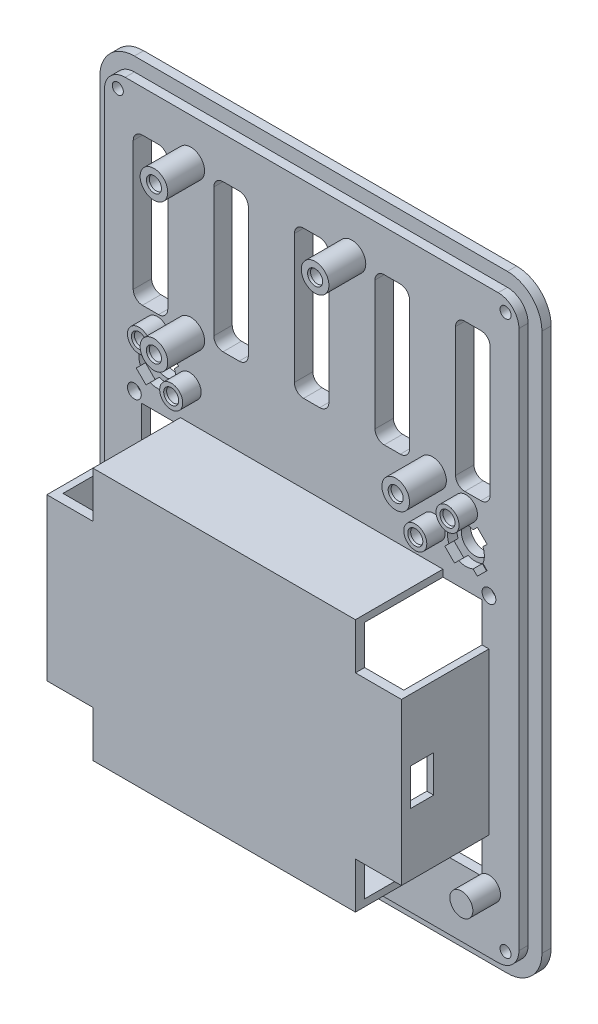
SolidWorks part; units mm, degrees
note: The reader was unsure of these and kept them because the rebuilt part matched: shared geometry of "Sketch8<3>", "Sketch17<3>", "Sketch16<3>".
ref_plane "Front Plane" through (0, 0, 0) normal (0, 0, 1) x (1, 0, 0)
ref_plane "Top Plane" through (0, 0, 0) normal (0, 1, 0) x (1, 0, 0)
ref_plane "Right Plane" through (0, 0, 0) normal (1, 0, 0) x (0, 0, -1)
sketch "Sketch2" plane through (0, 0, 0) normal (0, 0, 1) x (1, 0, 0)
  line L20 (45, -58.5) -> (45, 58.5)
  line L21 (-40.5, -63) -> (40.5, -63)
  line L22 (-45, 58.5) -> (-45, -58.5)
  line L23 (40.5, 63) -> (-40.5, 63)
  line L24 (45, -58.5) -> (45, 58.5)
  line L25 (-40.5, -63) -> (40.5, -63)
  line L26 (-45, 58.5) -> (-45, -58.5)
  line L27 (40.5, 63) -> (-40.5, 63)
  arc A24 (40.5, -63) -> (45, -58.5) centre (40.5, -58.5) ccw
  arc A25 (-45, -58.5) -> (-40.5, -63) centre (-40.5, -58.5) ccw
  arc A26 (-40.5, 63) -> (-45, 58.5) centre (-40.5, 58.5) ccw
  arc A27 (45, 58.5) -> (40.5, 63) centre (40.5, 58.5) ccw
  arc A28 (40.5, -63) -> (45, -58.5) centre (40.5, -58.5) ccw
  arc A29 (-45, -58.5) -> (-40.5, -63) centre (-40.5, -58.5) ccw
  arc A30 (-40.5, 63) -> (-45, 58.5) centre (-40.5, 58.5) ccw
  arc A31 (45, 58.5) -> (40.5, 63) centre (40.5, 58.5) ccw
  dimension "D1" = 3
extrude "Boss-Extrude1" add sketch "Sketch2" along normal blind 2
sketch "Sketch3" plane through (0, 0, 0) normal (0, 0, -1) x (-1, 0, 0)
  line L8 (-40.5, -66) -> (40.5, -66)
  line L9 (48, -58.5) -> (48, 58.5)
  line L10 (40.5, 66) -> (-40.5, 66)
  line L11 (-48, 58.5) -> (-48, -58.5)
  line L12 (-40.5, -66) -> (40.5, -66)
  line L13 (48, -58.5) -> (48, 58.5)
  line L14 (40.5, 66) -> (-40.5, 66)
  line L15 (-48, 58.5) -> (-48, -58.5)
  arc A8 (-48, -58.5) -> (-40.5, -66) centre (-40.5, -58.5) ccw
  arc A9 (40.5, -66) -> (48, -58.5) centre (40.5, -58.5) ccw
  arc A10 (48, 58.5) -> (40.5, 66) centre (40.5, 58.5) ccw
  arc A11 (-40.5, 66) -> (-48, 58.5) centre (-40.5, 58.5) ccw
  arc A12 (-48, -58.5) -> (-40.5, -66) centre (-40.5, -58.5) ccw
  arc A13 (40.5, -66) -> (48, -58.5) centre (40.5, -58.5) ccw
  arc A14 (48, 58.5) -> (40.5, 66) centre (40.5, 58.5) ccw
  arc A15 (-40.5, 66) -> (-48, 58.5) centre (-40.5, 58.5) ccw
  dimension "D1" = 3
extrude "Boss-Extrude2" add sketch "Sketch3" along normal blind 2
sketch "Sketch5" plane through (0, 0, -2) normal (0, 0, -1) x (-1, 0, 0)
  line L0 (-48, 38) -> (48, 38) construction
  line L1 (-36.75, 22) -> (-33.25, 22)
  line L2 (-38.75, 24) -> (-38.75, 52)
  line L3 (-36.75, 54) -> (-33.25, 54)
  line L4 (-31.25, 24) -> (-31.25, 52)
  line L5 (-38.75, 22) -> (-31.25, 54) construction
  line L6 (-38.75, 54) -> (-31.25, 22) construction
  line L7 (-48, 58.5) -> (-48, -58.5) construction
  line L8 (48, -58.5) -> (48, 58.5) construction
  line L9 (40.5, 66) -> (-40.5, 66) construction
  line L10 (-21.25, 24) -> (-21.25, 52)
  line L11 (-13.75, 24) -> (-13.75, 52)
  line L12 (-19.25, 54) -> (-15.75, 54)
  line L13 (-19.25, 22) -> (-15.75, 22)
  line L14 (-21.25, 54) -> (-13.75, 22) construction
  line L15 (-21.25, 22) -> (-13.75, 54) construction
  line L16 (-3.75, 24) -> (-3.75, 52)
  line L17 (3.75, 24) -> (3.75, 52)
  line L18 (-1.75, 54) -> (1.75, 54)
  line L19 (-1.75, 22) -> (1.75, 22)
  line L20 (-3.75, 54) -> (3.75, 22) construction
  line L21 (-3.75, 22) -> (3.75, 54) construction
  line L22 (13.75, 24) -> (13.75, 52)
  line L23 (21.25, 24) -> (21.25, 52)
  line L24 (15.75, 54) -> (19.25, 54)
  line L25 (15.75, 22) -> (19.25, 22)
  line L26 (13.75, 54) -> (21.25, 22) construction
  line L27 (13.75, 22) -> (21.25, 54) construction
  line L28 (31.25, 24) -> (31.25, 52)
  line L29 (38.75, 24) -> (38.75, 52)
  line L30 (33.25, 54) -> (36.75, 54)
  line L31 (33.25, 22) -> (36.75, 22)
  line L32 (31.25, 54) -> (38.75, 22) construction
  line L33 (31.25, 22) -> (38.75, 54) construction
  line L34 (-3.5, 66) -> (-3.5, 34) construction
  arc A0 (31.25, 52) -> (33.25, 54) centre (33.25, 52) cw
  arc A1 (38.75, 52) -> (36.75, 54) centre (36.75, 52) ccw
  arc A2 (38.75, 24) -> (36.75, 22) centre (36.75, 24) cw
  arc A3 (31.25, 24) -> (33.25, 22) centre (33.25, 24) ccw
  arc A4 (13.75, 24) -> (15.75, 22) centre (15.75, 24) ccw
  arc A5 (21.25, 24) -> (19.25, 22) centre (19.25, 24) cw
  arc A6 (21.25, 52) -> (19.25, 54) centre (19.25, 52) ccw
  arc A7 (13.75, 52) -> (15.75, 54) centre (15.75, 52) cw
  arc A8 (3.75, 24) -> (1.75, 22) centre (1.75, 24) cw
  arc A9 (-3.75, 24) -> (-1.75, 22) centre (-1.75, 24) ccw
  arc A10 (3.75, 52) -> (1.75, 54) centre (1.75, 52) ccw
  arc A11 (-3.75, 52) -> (-1.75, 54) centre (-1.75, 52) cw
  arc A12 (-21.25, 24) -> (-19.25, 22) centre (-19.25, 24) ccw
  arc A13 (-13.75, 24) -> (-15.75, 22) centre (-15.75, 24) cw
  arc A14 (-13.75, 52) -> (-15.75, 54) centre (-15.75, 52) ccw
  arc A15 (-21.25, 52) -> (-19.25, 54) centre (-19.25, 52) cw
  arc A16 (-33.25, 22) -> (-31.25, 24) centre (-33.25, 24) ccw
  arc A17 (-36.75, 22) -> (-38.75, 24) centre (-36.75, 24) cw
  arc A18 (-33.25, 54) -> (-31.25, 52) centre (-33.25, 52) cw
  arc A19 (-38.75, 52) -> (-36.75, 54) centre (-36.75, 52) cw
  point P0 (-35, 38)
  point P13 (-17.5, 38)
  point P19 (0, 38)
  point P24 (17.5, 38)
  point P29 (35, 38)
  dimension "D6" = 2
  dimension "D1" = 7.5
  dimension "D2" = 32
  dimension "D3" = 28
  dimension "D5" = 10
  dimension "D4" = 5
extrude "Cut-Extrude1" cut sketch "Sketch5" against normal through all
hole_wizard "CBORE for M2 Pan Head Machine Screw1" positions "Sketch7" profile "Sketch6" counterbore size "M2" standard "ANSI Metric" end condition through all
sketch "Sketch7" plane through (0, 0, -2) normal (0, 0, -1) x (-1, 0, 0)
  point P0 (-42.1, 60.1)
  point P3 (42.1, 60.1)
  point P6 (-42.1, -60.1)
  point P9 (42.1, -60.1)
sketch "Sketch6" plane through (42.1, 60.1, -2) normal (1, 0, 0) x (0, 1, 0)
  line L0 (0, 0) -> (0, 4)
  line L1 (0, 4) -> (1.2, 4)
  line L3 (1.2, 4) -> (1.2, 1.6)
  line L4 (1.2, 1.6) -> (2.5, 1.6)
  line L5 (2.5, 1.6) -> (2.5, 0)
  line L7 (2.5, 0) -> (0, 0)
  line L11 (0, -6.35) -> (0, 107.95) construction
  dimension "Thru Hole Dia." = 2.4
  dimension "Thru Hole Depth" = 4
  dimension "C'Bore Dia." = 5
  dimension "C'Bore Depth" = 1.6
sketch "Sketch8" plane through (0, 0, -2) normal (0, 0, -1) x (-1, 0, 0)
  line L0 (0, 66) -> (0, -66) construction
  line L1 (-37, 3.5) -> (37, 3.5)
  line L2 (-37, 3.5) -> (-37, -48.5)
  line L3 (-37, -48.5) -> (37, -48.5)
  line L4 (37, 3.5) -> (37, -48.5)
  line L5 (-37, 3.5) -> (37, -48.5) construction
  line L6 (-37, -48.5) -> (37, 3.5) construction
  line L7 (40.5, 66) -> (-40.5, 66) construction
  line L8 (-40.5, -66) -> (40.5, -66) construction
  line L9 (-38.5, 5) -> (38.5, 5)
  line L10 (38.5, 5) -> (38.5, -50)
  line L11 (-38.5, -50) -> (38.5, -50)
  line L12 (-38.5, 5) -> (-38.5, -50)
  point P0 (0, -22.5)
  dimension "D1" = 17.5
  dimension "D2" = 52
  dimension "D3" = 74
  dimension "D4" = 1.5
extrude "Boss-Extrude3" add sketch "Sketch8<3>" against normal blind 19 from surface at -4 contours L9 L10 L11 L12 starting at face at (40.9, 60.1, 2)
sketch "Sketch8<3>" plane through (0, 0, -2) normal (0, 0, -1) x (-1, 0, 0) same geometry as "Sketch8"
extrude "Cut-Extrude2" cut sketch "Sketch8" against normal blind 21 contours L1 L4 L3 L2
sketch "Sketch9" plane through (0, 0, -2) normal (0, 0, -1) x (-1, 0, 0)
  line L18 (-41, -52.5) -> (41, -52.5)
  line L19 (41, -52.5) -> (41, 7.5)
  line L20 (-41, 7.5) -> (-41, -52.5)
  line L21 (41, 7.5) -> (-41, 7.5)
  line L22 (-41, -52.5) -> (41, -52.5)
  line L23 (41, -52.5) -> (41, 7.5)
  line L24 (-41, 7.5) -> (-41, -52.5)
  line L25 (41, 7.5) -> (-41, 7.5)
  dimension "D1" = 4
extrude "Cut-Extrude3" cut sketch "Sketch9" against normal blind 2
sketch "Sketch10" plane through (0, 0, 2) normal (0, 0, 1) x (1, 0, 0)
  circle A0 centre (38.5, 5) radius 2.5
  circle A1 centre (-38.5, 5) radius 2.5
  circle A2 centre (-38.5, -50) radius 2.5
  circle A3 centre (38.5, -50) radius 2.5
  dimension "D1" = 5
sketch "Sketch30" plane through (0, 0, 2) normal (0, 0, 1) x (1, 0, 0)
  circle A0 centre (-38.5, 5) radius 1.5
  circle A1 centre (38.5, 5) radius 1.5
  dimension "D1" = 3
extrude "Cut-Extrude11" cut sketch "Sketch30" along normal blind 5 and the other way through all
sketch "Sketch15" plane through (38.5, 0, 0) normal (1, 0, 0) x (0, 0, -1)
  line L0 (-2, -22.5) -> (-21, -22.5) construction
  line L1 (-19, -18.5) -> (-14, -18.5)
  line L2 (-19, -18.5) -> (-19, -26.5)
  line L3 (-19, -26.5) -> (-14, -26.5)
  line L4 (-14, -18.5) -> (-14, -26.5)
  line L6 (-19, 3.5) -> (-19, -48.5) construction
  line L7 (-2, -50) -> (-2, 3.5) construction
  line L9 (-21, -50) -> (-21, 5) construction
  point P12 (-19, -22.5)
  dimension "D1" = 8
  dimension "D2" = 5
extrude "Cut-Extrude4" cut sketch "Sketch15" against normal through all
sketch "Sketch16" plane through (0, 0, -2) normal (0, 0, -1) x (-1, 0, 0)
  line L0 (2.5158, -57.4) -> (-2.5158, -57.4)
  line L1 (-4, -54.9) -> (-4, -55.719)
  line L2 (3.5, -54.4) -> (-3.5, -54.4)
  line L3 (4, -54.9) -> (4, -55.719)
  line L4 (0, -54.4) -> (0, -57.4) construction
  line L5 (-3.8841, -56.0391) -> (-2.8999, -57.2201)
  line L6 (3.8841, -56.0391) -> (2.8999, -57.2201)
  line L7 (0, 66) -> (0, -66) construction
  line L8 (40.5, 66) -> (-40.5, 66) construction
  line L9 (-40.5, -66) -> (40.5, -66) construction
  line L10 (40.5, -63) -> (-40.5, -63) construction
  line L12 (6.5, -59.2) -> (-6.5, -59.2)
  line L13 (6.5, -59.2) -> (6.5, -53.4)
  line L14 (6.5, -53.4) -> (-6.5, -53.4)
  line L15 (-6.5, -59.2) -> (-6.5, -53.4)
  line L16 (6.5, -59.2) -> (-6.5, -53.4) construction
  line L17 (6.5, -53.4) -> (-6.5, -59.2) construction
  arc A0 (-4, -55.719) -> (-3.8841, -56.0391) centre (-3.5, -55.719) ccw
  arc A1 (-2.5158, -57.4) -> (-2.8999, -57.2201) centre (-2.5158, -56.9) cw
  arc A2 (2.5158, -57.4) -> (2.8999, -57.2201) centre (2.5158, -56.9) ccw
  arc A3 (4, -55.719) -> (3.8841, -56.0391) centre (3.5, -55.719) cw
  arc A4 (4, -54.9) -> (3.5, -54.4) centre (3.5, -54.9) ccw
  arc A5 (-3.5, -54.4) -> (-4, -54.9) centre (-3.5, -54.9) ccw
  point P7 (0, -55.9)
  point P19 (-4, -55.9)
  point P22 (-2.75, -57.4)
  point P25 (2.75, -57.4)
  point P30 (4, -54.4)
  point P33 (-4, -54.4)
  point P34 (0, -55.9)
  point P39 (0, -56.3)
  point P40 (0, -56.3)
  point P41 (0, -56.3)
  dimension "D6" = 0.5
  dimension "D8" = 13
  dimension "D7" = 1.8
  dimension "D1" = 8
  dimension "D2" = 5.5
  dimension "D3" = 3
  dimension "D4" = 1.5
  dimension "D5" = 5.6
  dimension "D9" = 1
extrude "Cut-Extrude5" cut sketch "Sketch16" against normal through all contours L2 A5 L1 A0 L5 A1 L0 A2 L6 A3 L3 A4
sketch "Sketch17" plane through (0, 0, 0) normal (0, 0, -1) x (-1, 0, 0)
  line L0 (-28.9038, 9.5251) -> (-29.8173, 10.4386)
  line L1 (38.0962, 9.5251) -> (37.1827, 10.4386)
  line L2 (38.0962, 9.5251) -> (35.9749, 7.4038)
  line L3 (31.0251, 16.5962) -> (28.9038, 14.4749)
  line L4 (37.1827, 13.5614) -> (38.0962, 14.4749)
  line L5 (35.9749, 7.4038) -> (35.0614, 8.3173)
  line L6 (31.9386, 15.6827) -> (31.0251, 16.5962)
  line L7 (38.0962, 9.5251) -> (28.9038, 14.4749) construction
  line L8 (35.0614, 15.6827) -> (35.9749, 16.5962)
  line L9 (31.0251, 16.5962) -> (35.9749, 7.4038) construction
  line L10 (29.9376, 12) -> (-56.7892, 12) construction
  line L11 (28.9038, 9.5251) -> (29.8173, 10.4386)
  line L12 (28.9038, 9.5251) -> (31.0251, 7.4038)
  line L13 (35.9749, 16.5962) -> (38.0962, 14.4749)
  line L14 (31.0251, 7.4038) -> (31.9386, 8.3173)
  line L15 (28.9038, 9.5251) -> (38.0962, 14.4749) construction
  line L16 (35.9749, 16.5962) -> (31.0251, 7.4038) construction
  line L17 (-28.9038, 9.5251) -> (-31.0251, 7.4038)
  line L18 (33.5, 5) -> (33.5, 12) construction
  line L19 (37, 5) -> (-37, 5) construction
  line L20 (29.8173, 13.5614) -> (28.9038, 14.4749)
  line L21 (-35.9749, 16.5962) -> (-38.0962, 14.4749)
  line L22 (-31.0251, 7.4038) -> (-31.9386, 8.3173)
  line L23 (-28.9038, 9.5251) -> (-38.0962, 14.4749) construction
  line L24 (-35.9749, 16.5962) -> (-31.0251, 7.4038) construction
  line L25 (-35.9749, 7.4038) -> (-35.0614, 8.3173)
  line L26 (-35.9749, 7.4038) -> (-38.0962, 9.5251)
  line L27 (-28.9038, 14.4749) -> (-31.0251, 16.5962)
  line L28 (-38.0962, 9.5251) -> (-37.1827, 10.4386)
  line L29 (-35.9749, 7.4038) -> (-31.0251, 16.5962) construction
  line L30 (-28.9038, 14.4749) -> (-38.0962, 9.5251) construction
  line L31 (-29.8173, 13.5614) -> (-28.9038, 14.4749)
  line L32 (-35.0614, 15.6827) -> (-35.9749, 16.5962)
  line L33 (-37.1827, 13.5614) -> (-38.0962, 14.4749)
  line L34 (-31.9386, 15.6827) -> (-31.0251, 16.5962)
  line L35 (-33.5, 5) -> (-33.5, 12) construction
  line L36 (37, 5) -> (-37, 5) construction
  line L37 (-38.5, -50) -> (-38.5, 3.5) construction
  circle A0 centre (33.5, 12) radius 3
  circle A1 centre (-33.5, 12) radius 3
  arc A2 (29.8173, 13.5614) -> (29.8173, 10.4386) centre (33.5, 12) ccw
  arc A3 (37.1827, 10.4386) -> (37.1827, 13.5614) centre (33.5, 12) ccw
  circle A4 centre (33.5, 12) radius 4 construction
  arc A5 (35.0614, 15.6827) -> (31.9386, 15.6827) centre (33.5, 12) ccw
  arc A6 (31.9386, 8.3173) -> (35.0614, 8.3173) centre (33.5, 12) ccw
  arc A7 (-31.9386, 15.6827) -> (-35.0614, 15.6827) centre (-33.5, 12) ccw
  arc A8 (-29.8173, 10.4386) -> (-29.8173, 13.5614) centre (-33.5, 12) ccw
  circle A9 centre (-33.5, 12) radius 4 construction
  arc A10 (-37.1827, 13.5614) -> (-37.1827, 10.4386) centre (-33.5, 12) ccw
  arc A11 (-35.0614, 8.3173) -> (-31.9386, 8.3173) centre (-33.5, 12) ccw
  arc A12 (38.5, 3.5) -> (37, 5) centre (38.5, 5) ccw construction
  point P9 (33.5, 12)
  point P13 (40.5, -3)
  point P18 (-33.5, 12)
  point P20 (-38.5, 12)
  point P23 (42.3252, 13.1695)
  point P25 (44, -3)
  point P34 (-36, -3)
  point P36 (-34.2282, 12)
  dimension "D2" = 6
  dimension "D1" = 3
  dimension "D3" = 10
  dimension "D4" = 1
  dimension "D5" = 45
  dimension "D7" = 45
  dimension "D8" = 1
  dimension "D9" = 10
  dimension "D10" = 10
  dimension "D11" = 5
  dimension "D6" = 7
  dimension "D12" = 5
extrude "Cut-Extrude7" cut sketch "Sketch17" along normal up to surface (2 mm away) and the other way through all contours A0 | A1 up to face at (0, -55.9379, -2)
extrude "Cut-Extrude8" cut sketch "Sketch17<3>" along normal blind 2 from surface at -2 starting at face at (36.5, 12, 2)
sketch "Sketch17<3>" plane through (0, 0, 0) normal (0, 0, -1) x (-1, 0, 0) same geometry as "Sketch17"
sketch "Sketch18" [suppressed] plane through (0, 0, 2) normal (0, 0, 1) x (1, 0, 0)
  line L0 (-40.5, 5) -> (-40.5, -11) construction
  line L1 (-40.5, 5) -> (40.5, 5) construction
  line L2 (-40.5, -11) -> (40.5, -11) construction
  line L3 (40.5, -11) -> (40.5, 5) construction
  circle A0 centre (-40.5, 5) radius 2.5
  circle A1 centre (-40.5, -11) radius 2.5
  circle A3 centre (40.5, 5) radius 2.5
  circle A4 centre (40.5, -11) radius 2.5
  point P5 (-40.5, -3)
  point P13 (40.5, -3)
  dimension "D1" = 5
  dimension "D2" = 16
  dimension "D3" = 8
extrude "Boss-Extrude5" [suppressed] add sketch "Sketch18" along normal blind 4
hole_wizard "CSK for M2 Flat Head Machine Screw4" [suppressed] positions "3DSketch2" profile "Sketch20" countersink size "M2" standard "ANSI Metric"
sketch3d "3DSketch2"
  line L0 (40.5, 5, 6) -> (40.5, 5, 2) construction
  line L1 (40.5, -11, 6) -> (40.5, -11, 2) construction
  line L2 (-40.5, 5, 6) -> (-40.5, 5, 2) construction
  line L3 (-40.5, -11, 6) -> (-40.5, -11, 2) construction
  point P0 (40.5, 5, 6)
  point P4 (40.5, -11, 6)
  point P8 (-40.5, 5, 6)
  point P12 (-40.5, -11, 6)
sketch "Sketch20" plane through (40.5, 5, 6) normal (1, 0, 0) x (0, -1, 0)
  line L0 (0, 0) -> (0, 6)
  line L1 (0, 6) -> (1.5, 6)
  line L2 (1.5, 6) -> (1.5, 0.5038)
  line L3 (1.5, 0.5038) -> (1.635, 0)
  line L5 (1.635, 0) -> (0, 0)
  line L6 (-1.5, 0.5038) -> (-1.635, 0) construction
  line L10 (0, 6) -> (-1.5, 6) construction
  line L11 (0, -6.35) -> (0, 107.95) construction
  dimension "Hole Dia." = 3
  dimension "Hole Depth" = 6
  dimension "Near C'Sink Dia." = 3.27
  dimension "Near C'Sink Angle" = 30
  dimension "Drill Angle" = 180
extrude "Cut-Extrude9" cut sketch "Sketch16<3>" along normal blind 3 from surface at -4 starting at face at (33.5, 12, 2)
sketch "Sketch16<3>" plane through (0, 0, -2) normal (0, 0, -1) x (-1, 0, 0) same geometry as "Sketch16"
sketch "Sketch21" plane through (0, 0, 2) normal (0, 0, 1) x (1, 0, 0)
  line L0 (-33.5, 19) -> (-33.5, 12) construction
  line L1 (-33.5, 12) -> (-26.5, 12) construction
  line L2 (33.5, 19) -> (33.5, 12) construction
  line L3 (33.5, 12) -> (26.5, 12) construction
  circle A0 centre (-26.5, 12) radius 2.5
  circle A1 centre (-33.5, 19) radius 2.5
  circle A2 centre (26.5, 12) radius 2.5
  circle A3 centre (33.5, 19) radius 2.5
  dimension "D1" = 5
  dimension "D2" = 7
  dimension "D3" = 7
  dimension "D4" = 7
  dimension "D5" = 7
extrude "Boss-Extrude6" add sketch "Sketch21" along normal blind 4
hole_wizard "CSK for M2 Flat Head Machine Screw5" positions "Sketch23" profile "Sketch22" countersink size "M2" standard "ANSI Metric"
sketch "Sketch23" plane through (0, 0, 6) normal (0, 0, 1) x (1, 0, 0)
  point P0 (-33.5, 19)
  point P3 (-26.5, 12)
  point P6 (26.5, 12)
  point P9 (33.5, 19)
sketch "Sketch22" plane through (-33.5, 19, 6) normal (1, 0, 0) x (0, -1, 0)
  line L0 (0, 0) -> (0, 4)
  line L1 (0, 4) -> (1.5, 4)
  line L2 (1.5, 4) -> (1.5, 0.5038)
  line L3 (1.5, 0.5038) -> (1.635, 0)
  line L5 (1.635, 0) -> (0, 0)
  line L6 (-1.5, 0.5038) -> (-1.635, 0) construction
  line L10 (0, 4) -> (-1.5, 4) construction
  line L11 (0, -6.35) -> (0, 107.95) construction
  dimension "Hole Dia." = 3
  dimension "Hole Depth" = 4
  dimension "Near C'Sink Dia." = 3.27
  dimension "Near C'Sink Angle" = 30
  dimension "Drill Angle" = 180
sketch "Sketch27" plane through (0, 0, 2) normal (0, 0, 1) x (1, 0, 0)
  line L0 (-26.25, 54) -> (26.25, 54) construction
  line L1 (26.25, 54) -> (26.25, 22) construction
  line L2 (26.25, 22) -> (-26.25, 22) construction
  line L3 (-26.25, 22) -> (-26.25, 54) construction
  line L4 (-21.25, 24) -> (-21.25, 52) construction
  line L7 (-1.75, 54) -> (1.75, 54) construction
  line L8 (21.25, 52) -> (21.25, 24) construction
  line L9 (-15.75, 22) -> (-19.25, 22) construction
  line L10 (3.75, 52) -> (3.75, 24) construction
  circle A0 centre (-26.25, 54) radius 3
  circle A1 centre (-26.25, 22) radius 3
  circle A2 centre (8.75, 54) radius 3
  circle A3 centre (26.25, 22) radius 3
  dimension "D1" = 6
  dimension "D2" = 5
  dimension "D3" = 5
  dimension "D4" = 5
extrude "Boss-Extrude7" add sketch "Sketch27" along normal blind 8
hole_wizard "CSK for M2 Flat Head Machine Screw6" positions "Sketch29" profile "Sketch28" countersink size "M2" standard "ANSI Metric"
sketch "Sketch29" plane through (0, 0, 10) normal (0, 0, 1) x (1, 0, 0)
  point P0 (-26.25, 54)
  point P3 (8.75, 54)
  point P6 (-26.25, 22)
  point P9 (26.25, 22)
sketch "Sketch28" plane through (-26.25, 54, 10) normal (1, 0, 0) x (0, -1, 0)
  line L0 (0, 0) -> (0, 8)
  line L1 (0, 8) -> (1.5, 8)
  line L2 (1.5, 8) -> (1.5, 0.5038)
  line L3 (1.5, 0.5038) -> (1.635, 0)
  line L5 (1.635, 0) -> (0, 0)
  line L6 (-1.5, 0.5038) -> (-1.635, 0) construction
  line L10 (0, 8) -> (-1.5, 8) construction
  line L11 (0, -6.35) -> (0, 107.95) construction
  dimension "Hole Dia." = 3
  dimension "Hole Depth" = 8
  dimension "Near C'Sink Dia." = 3.27
  dimension "Near C'Sink Angle" = 30
  dimension "Drill Angle" = 180
sketch "Sketch31" plane through (0, 0, 21) normal (0, 0, 1) x (1, 0, 0)
  line L0 (-37, -26.5) -> (-37, -48.5) construction
  line L1 (-38.5, 5) -> (-28.5, 5)
  line L2 (-38.5, 5) -> (-38.5, -5)
  line L3 (-38.5, -5) -> (-28.5, -5)
  line L4 (-28.5, 5) -> (-28.5, -5)
  line L5 (38.5, 5) -> (28.5, 5)
  line L6 (38.5, 5) -> (38.5, -5)
  line L7 (38.5, -5) -> (28.5, -5)
  line L8 (28.5, 5) -> (28.5, -5)
  line L9 (-38.5, -50) -> (-28.5, -50)
  line L10 (-38.5, -50) -> (-38.5, -40)
  line L11 (-38.5, -40) -> (-28.5, -40)
  line L12 (-28.5, -50) -> (-28.5, -40)
  line L13 (38.5, -50) -> (28.5, -50)
  line L14 (38.5, -50) -> (38.5, -40)
  line L15 (38.5, -40) -> (28.5, -40)
  line L16 (28.5, -50) -> (28.5, -40)
  line L17 (37, -48.5) -> (-37, -48.5) construction
  line L18 (37, -26.5) -> (37, -48.5) construction
  dimension "D1" = 10
  dimension "D2" = 1.5
  dimension "D3" = 1.5
  dimension "D4" = 1.5
  dimension "D5" = 1.5
extrude "Cut-Extrude12" cut sketch "Sketch31" against normal up to surface (19 mm away) up to face at (11.75, 54, 2)
extrude "Boss-Extrude8" add sketch "Sketch10" along normal blind 6 contours A2 | A3
hole_wizard "CSK for M2 Flat Head Machine Screw2" positions "Sketch14" profile "Sketch13" countersink size "M2" standard "ANSI Metric"
sketch "Sketch14" plane through (0, 0, 0) normal (0, 0, -1) x (-1, 0, 0)
  line L0 (37, -48.5) -> (-37, -48.5) construction
  line L1 (-37, -48.5) -> (-37, 3.5) construction
  line L2 (37, -48.5) -> (37, 3.5) construction
  point P16 (-38.5, -50)
  point P19 (38.5, -50)
  dimension "D1" = 1.5
  dimension "D2" = 1.5
  dimension "D3" = 1.5
  dimension "D4" = 1.5
sketch "Sketch13" plane through (38.5, -50, 0) normal (1, 0, 0) x (0, 1, 0)
  line L0 (0, 0) -> (0, 6.9013)
  line L1 (0, 6.9013) -> (1.5, 6)
  line L2 (1.5, 6) -> (1.5, 0.5038)
  line L3 (1.5, 0.5038) -> (1.635, 0)
  line L5 (1.635, 0) -> (0, 0)
  line L6 (-1.5, 0.5038) -> (-1.635, 0) construction
  line L10 (0, 6.9013) -> (-1.5, 6) construction
  line L11 (0, -6.35) -> (0, 107.95) construction
  dimension "Hole Dia." = 3
  dimension "Hole Depth" = 6
  dimension "Near C'Sink Dia." = 3.27
  dimension "Near C'Sink Angle" = 30
  dimension "Drill Angle" = 118
